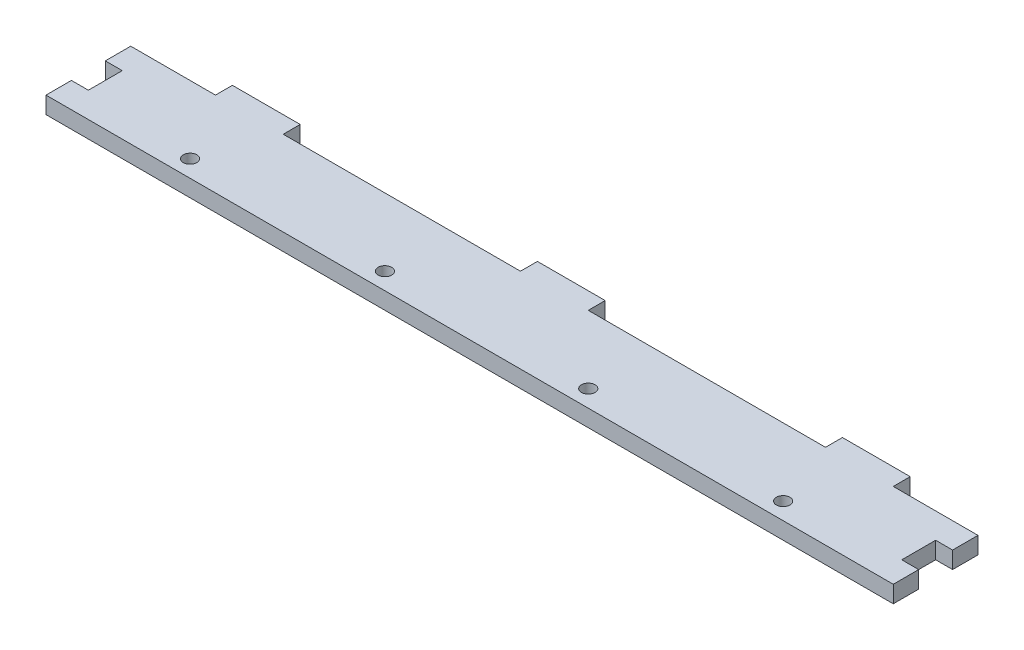
SolidWorks part; units mm, degrees
ref_plane "Front Plane" through (0, 0, 0) normal (0, 0, 1) x (1, 0, 0)
ref_plane "Top Plane" through (0, 0, 0) normal (0, 1, 0) x (1, 0, 0)
ref_plane "Right Plane" through (0, 0, 0) normal (1, 0, 0) x (0, 0, -1)
sketch "Sketch1" plane through (0, 0, 0) normal (0, 1, 0) x (1, 0, 0)
  line L0 (0, -12.5) -> (0, 15) construction
  line L1 (-125, 12.5) -> (-100, 12.5)
  line L2 (-125, 12.5) -> (-125, 5)
  line L3 (-125, -12.5) -> (125, -12.5)
  line L4 (125, 12.5) -> (125, 5)
  line L5 (-125, 12.5) -> (125, -12.5) construction
  line L6 (-125, -12.5) -> (125, 12.5) construction
  line L7 (100, 17.5) -> (80, 17.5)
  line L9 (-100, 12.5) -> (-100, 17.5)
  line L10 (-100, 17.5) -> (-80, 17.5)
  line L11 (-80, 12.5) -> (-80, 17.5)
  line L12 (80, 12.5) -> (80, 17.5)
  line L14 (100, 12.5) -> (100, 17.5)
  line L15 (-80, 12.5) -> (-10, 12.5)
  line L16 (100, 12.5) -> (125, 12.5)
  line L17 (10, 12.5) -> (80, 12.5)
  line L18 (-10, 17.5) -> (10, 17.5)
  line L19 (-10, 17.5) -> (-10, 12.5)
  line L21 (10, 17.5) -> (10, 12.5)
  line L22 (-10, 17.5) -> (10, 12.5) construction
  line L23 (-10, 12.5) -> (10, 17.5) construction
  line L24 (-125, -7.5) -> (125, -7.5) construction
  line L25 (120, 5) -> (125, 5)
  line L26 (-120, -5) -> (-125, -5)
  line L27 (-120, -5) -> (-120, 5)
  line L28 (-120, 5) -> (-125, 5)
  line L29 (-125, -5) -> (-125, 5) construction
  line L30 (-120, -5) -> (-125, 5) construction
  line L31 (-120, 5) -> (-125, -5) construction
  line L32 (125, -5) -> (125, 5) construction
  line L33 (120, -5) -> (125, -5)
  line L34 (120, -5) -> (120, 5)
  line L35 (-125, 5) -> (-125, -5) construction
  line L36 (-125, -5) -> (-125, -12.5)
  line L37 (125, 5) -> (125, -5) construction
  line L38 (125, -5) -> (125, -12.5)
  circle A0 centre (-30, -7.5) radius 2
  circle A1 centre (-87.5, -7.5) radius 2
  circle A2 centre (30, -7.5) radius 2
  circle A3 centre (87.5, -7.5) radius 2
  point P0 (0, 0)
  point P18 (0, 15)
  point P31 (-122.5, 0)
  point P36 (0, 0)
  dimension "D8" = 4
  dimension "D10" = 4
  dimension "D12" = 10
  dimension "D1" = 250
  dimension "D2" = 25
  dimension "D3" = 20
  dimension "D4" = 5
  dimension "D5" = 25
  dimension "D6" = 20
  dimension "D7" = 5
  dimension "D9" = 30
  dimension "D11" = 87.5
  dimension "D13" = 5
extrude "Boss-Extrude1" add sketch "Sketch1" along normal blind 5
